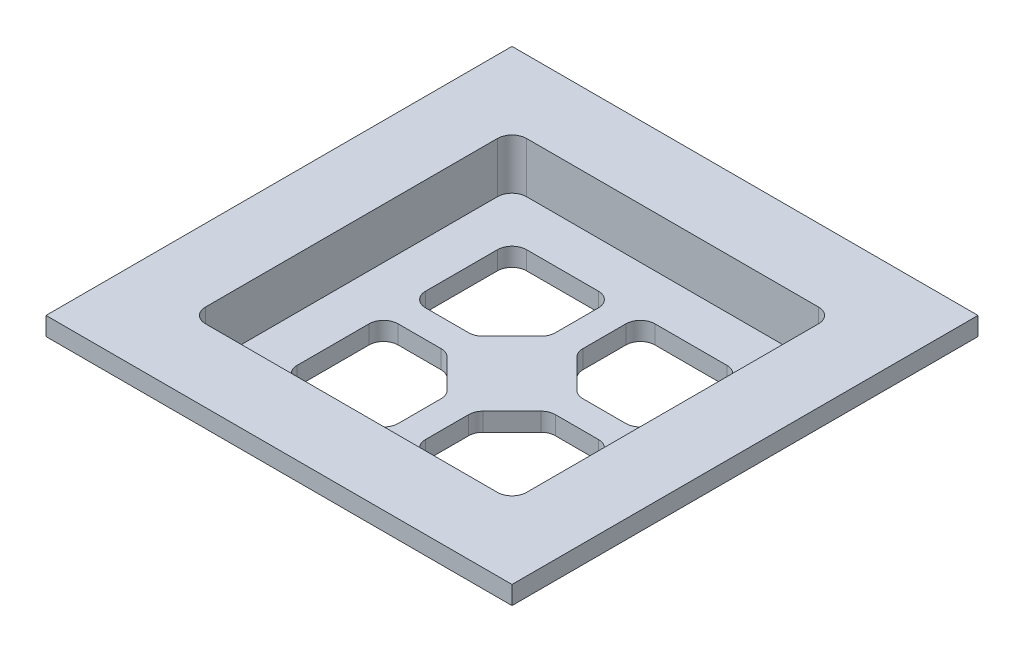
SolidWorks part; units mm, degrees
ref_plane "Front Plane" through (0, 0, 0) normal (0, 0, 1) x (1, 0, 0)
ref_plane "Top Plane" through (0, 0, 0) normal (0, 1, 0) x (1, 0, 0)
ref_plane "Right Plane" through (0, 0, 0) normal (1, 0, 0) x (0, 0, -1)
sketch "Sketch3" plane through (0, 0, 0) normal (0, 1, 0) x (1, 0, 0)
  line L1 (0, 0) -> (47.625, 0) construction
  line L3 (0, 47.625) -> (47.625, 47.625) construction
  line L8 (0, 47.625) -> (0, 0) construction
  line L9 (47.625, 47.625) -> (47.625, 0) construction
  line L14 (0.254, 0.254) -> (47.371, 0.254)
  line L15 (47.371, 47.371) -> (47.371, 0.254)
  line L16 (0.254, 47.371) -> (47.371, 47.371)
  line L17 (0.254, 47.371) -> (0.254, 0.254)
  point P9 (0, 47.625)
  point P12 (0, 0)
  dimension "D2" = 0.254
  dimension "D1" = 47.625
extrude "Boss-Extrude1" add sketch "Sketch3" along normal blind 5.5008
sketch "Sketch6" plane through (0, 5.5008, 0) normal (0, 1, 0) x (1, 0, 0)
  line L7 (22.3125, 36.3125) -> (22.3125, 25.3125)
  line L17 (25.3125, 36.3125) -> (25.3125, 25.3125)
  line L18 (25.3125, 25.3125) -> (36.3125, 25.3125)
  line L20 (25.3125, 22.3125) -> (36.3125, 22.3125)
  line L23 (22.3125, 22.3125) -> (22.3125, 11.3125)
  line L25 (25.3125, 22.3125) -> (25.3125, 11.3125)
  line L26 (11.3125, 25.3125) -> (22.3125, 25.3125)
  line L28 (36.3125, 11.3125) -> (36.3125, 22.3125)
  line L29 (11.3125, 11.3125) -> (22.3125, 11.3125)
  line L30 (11.3125, 36.3125) -> (11.3125, 25.3125)
  line L31 (36.3125, 36.3125) -> (25.3125, 36.3125)
  line L32 (11.3125, 22.3125) -> (22.3125, 22.3125)
  line L35 (11.3125, 22.3125) -> (11.3125, 11.3125)
  line L37 (25.3125, 11.3125) -> (36.3125, 11.3125)
  line L39 (36.3125, 25.3125) -> (36.3125, 36.3125)
  line L40 (22.3125, 36.3125) -> (11.3125, 36.3125)
  line L42 (23.8125, 47.371) -> (23.8125, 0.254) construction
  line L43 (47.371, 47.371) -> (0.254, 47.371) construction
  line L44 (0.254, 0.254) -> (47.371, 0.254) construction
  line L45 (0.254, 23.8125) -> (47.371, 23.8125) construction
  line L46 (0.254, 47.371) -> (0.254, 0.254) construction
  line L47 (47.371, 0.254) -> (47.371, 47.371) construction
  dimension "D2" = 11
  dimension "D7" = 3
  dimension "D8" = 1.5
  dimension "D9" = 1.5
  dimension "D10" = 1.5
  dimension "D11" = 1.5
extrude "Cut-Extrude2" cut sketch "Sketch6" against normal up to next
sketch "Sketch7" plane through (0, 5.5008, 0) normal (0, 1, 0) x (1, 0, 0)
  line L0 (23.8125, 41.3125) -> (23.8125, 47.371) construction
  line L1 (6.3125, 41.3125) -> (41.3125, 41.3125)
  line L2 (6.3125, 41.3125) -> (6.3125, 6.3125)
  line L3 (6.3125, 6.3125) -> (41.3125, 6.3125)
  line L4 (41.3125, 41.3125) -> (41.3125, 6.3125)
  line L5 (47.371, 47.371) -> (0.254, 47.371) construction
  line L6 (6.3125, 23.8125) -> (0.254, 23.8125) construction
  line L7 (0.254, 47.371) -> (0.254, 0.254) construction
  line L9 (-1.5875, 49.2125) -> (49.2125, 49.2125)
  line L10 (-1.5875, 49.2125) -> (-1.5875, -1.5875)
  line L11 (-1.5875, -1.5875) -> (49.2125, -1.5875)
  line L12 (49.2125, 49.2125) -> (49.2125, -1.5875)
  dimension "D1" = 35
  dimension "D2" = 7.9
  dimension "D3" = 7.9
  dimension "D4" = 50.8
extrude "Boss-Extrude2" add sketch "Sketch7" along normal blind 2
sketch "Sketch12" plane through (0, 5.5008, 0) normal (0, 1, 0) x (1, 0, 0)
  line L4 (41.3125, 41.3125) -> (6.3125, 41.3125)
  line L5 (6.3125, 41.3125) -> (6.3125, 6.3125)
  line L6 (6.3125, 6.3125) -> (41.3125, 6.3125)
  line L7 (41.3125, 6.3125) -> (41.3125, 41.3125)
  line L8 (41.3125, 41.3125) -> (6.3125, 41.3125)
  line L9 (6.3125, 41.3125) -> (6.3125, 6.3125)
  line L10 (6.3125, 6.3125) -> (41.3125, 6.3125)
  line L11 (41.3125, 6.3125) -> (41.3125, 41.3125)
  dimension "D1" = 0
extrude "Cut-Extrude3" cut sketch "Sketch12" against normal blind 3.5
sketch "Sketch11" plane through (0, 2.0008, 0) normal (0, 1, 0) x (1, 0, 0)
  line L0 (23.8125, 18.2414) -> (23.8125, 6.3125) construction
  line L1 (22.3125, 29.3836) -> (25.3125, 29.3836)
  line L2 (18.2414, 25.3125) -> (18.2414, 22.3125)
  line L3 (22.3125, 18.2414) -> (25.3125, 18.2414)
  line L4 (29.3836, 25.3125) -> (29.3836, 22.3125)
  line L5 (6.3125, 6.3125) -> (41.3125, 6.3125) construction
  line L6 (29.3836, 23.8125) -> (41.3125, 23.8125) construction
  line L8 (18.2414, 25.3125) -> (22.3125, 29.3836)
  line L10 (25.3125, 29.3836) -> (29.3836, 25.3125)
  line L12 (29.3836, 22.3125) -> (25.3125, 18.2414)
  line L13 (22.3125, 18.2414) -> (18.2414, 22.3125)
  line L20 (41.3125, 6.3125) -> (41.3125, 41.3125) construction
  line L21 (25.3125, 25.3125) -> (25.3125, 36.3125) construction
  line L22 (22.3125, 36.3125) -> (22.3125, 25.3125) construction
  line L23 (36.3125, 25.3125) -> (25.3125, 25.3125) construction
  line L24 (25.3125, 22.3125) -> (36.3125, 22.3125) construction
  line L25 (25.3125, 11.3125) -> (25.3125, 22.3125) construction
  line L26 (22.3125, 22.3125) -> (22.3125, 11.3125) construction
  line L27 (11.3125, 22.3125) -> (22.3125, 22.3125) construction
  line L28 (22.3125, 25.3125) -> (11.3125, 25.3125) construction
  point P0 (18.2219, 25.3125)
  dimension "D1" = 10
  dimension "D2" = 135
extrude "Boss-Extrude4" add sketch "Sketch11" against normal up to surface (2.0008 mm away) up to face at (30.8125, 0, -16.8125)
fillet "Fillet3" radius 1.5875 28 edges at (25.3125, 1.0004, -11.3125) (11.3125, 1.0004, -11.3125) (22.3125, 1.0004, -11.3125) (36.3125, 1.0004, -11.3125) (36.3125, 1.0004, -22.3125) (11.3125, 1.0004, -22.3125) (36.3125, 1.0004, -36.3125) (36.3125, 1.0004, -25.3125) (25.3125, 1.0004, -36.3125) (22.3125, 1.0004, -36.3125) (11.3125, 1.0004, -25.3125) (11.3125, 1.0004, -36.3125) (41.3125, 4.7508, -41.3125) (41.3125, 4.7508, -6.3125) (6.3125, 4.7508, -6.3125) (6.3125, 4.7508, -41.3125) (29.3836, 1.0004, -22.3125) (25.3125, 1.0004, -18.2414) (29.3836, 1.0004, -25.3125) (25.3125, 1.0004, -29.3836) (22.3125, 1.0004, -29.3836) (18.2414, 1.0004, -25.3125) (18.2414, 1.0004, -22.3125) (22.3125, 1.0004, -18.2414) (0.254, 2.7504, -47.371) (47.371, 2.7504, -47.371) (47.371, 2.7504, -0.254) (0.254, 2.7504, -0.254)
sketch "Sketch13" plane through (0, 0, 0) normal (0, -1, 0) x (1, 0, 0)
  line L0 (4.018, -5.6055) -> (4.018, -42.0195)
  line L1 (5.6055, -43.607) -> (42.0195, -43.607)
  line L2 (43.607, -42.0195) -> (43.607, -5.6055)
  line L3 (42.0195, -4.018) -> (5.6055, -4.018)
  line L4 (0.254, -1.8415) -> (0.254, -45.7835)
  line L5 (1.8415, -47.371) -> (45.7835, -47.371)
  line L6 (47.371, -45.7835) -> (47.371, -1.8415)
  line L7 (45.7835, -0.254) -> (1.8415, -0.254)
  line L8 (0.254, -1.8415) -> (0.254, -45.7835)
  line L9 (1.8415, -47.371) -> (45.7835, -47.371)
  line L10 (47.371, -45.7835) -> (47.371, -1.8415)
  line L11 (45.7835, -0.254) -> (1.8415, -0.254)
  line L12 (4.018, -4.018) -> (4.018, -43.607) construction
  line L13 (43.607, -4.018) -> (4.018, -4.018) construction
  line L14 (43.607, -43.607) -> (43.607, -4.018) construction
  line L15 (4.018, -43.607) -> (43.607, -43.607) construction
  arc A4 (0.254, -45.7835) -> (1.8415, -47.371) centre (1.8415, -45.7835) ccw
  arc A5 (45.7835, -47.371) -> (47.371, -45.7835) centre (45.7835, -45.7835) ccw
  arc A6 (47.371, -1.8415) -> (45.7835, -0.254) centre (45.7835, -1.8415) ccw
  arc A7 (1.8415, -0.254) -> (0.254, -1.8415) centre (1.8415, -1.8415) ccw
  arc A8 (0.254, -45.7835) -> (1.8415, -47.371) centre (1.8415, -45.7835) ccw
  arc A9 (45.7835, -47.371) -> (47.371, -45.7835) centre (45.7835, -45.7835) ccw
  arc A10 (47.371, -1.8415) -> (45.7835, -0.254) centre (45.7835, -1.8415) ccw
  arc A11 (1.8415, -0.254) -> (0.254, -1.8415) centre (1.8415, -1.8415) ccw
  arc A12 (43.607, -4.018) -> (43.607, -4.018) centre (43.607, -4.018) ccw construction
  arc A13 (4.018, -4.018) -> (4.018, -4.018) centre (4.018, -4.018) ccw construction
  arc A14 (4.018, -43.607) -> (4.018, -43.607) centre (4.018, -43.607) ccw construction
  arc A15 (43.607, -43.607) -> (43.607, -43.607) centre (43.607, -43.607) ccw construction
  arc A16 (4.018, -5.6055) -> (5.6055, -4.018) centre (5.6055, -5.6055) cw
  arc A17 (43.607, -5.6055) -> (42.0195, -4.018) centre (42.0195, -5.6055) ccw
  arc A18 (42.0195, -43.607) -> (43.607, -42.0195) centre (42.0195, -42.0195) ccw
  arc A19 (5.6055, -43.607) -> (4.018, -42.0195) centre (5.6055, -42.0195) cw
  point P24 (43.861, -43.861)
  point P25 (0, 0)
  point P26 (43.861, -43.861)
  point P27 (0, 0)
  point P28 (43.861, -3.764)
  point P29 (43.861, -3.764)
  point P30 (43.861, -43.861)
  point P31 (3.764, -43.861)
  point P32 (3.764, -3.764)
  point P33 (0, 0)
  point P35 (0, 0)
  point P36 (0, 0)
  point P38 (0, 0)
  dimension "D3" = 1.5875
  dimension "D4" = 1.5875
  dimension "D5" = 1.5875
  dimension "D6" = 1.5875
  dimension "D1" = 0
  dimension "D2" = 3.764
extrude "Cut-Extrude5" cut sketch "Sketch13" against normal up to surface (5.5008 mm away) up to face at (23.8125, 5.5008, -23.8125)
